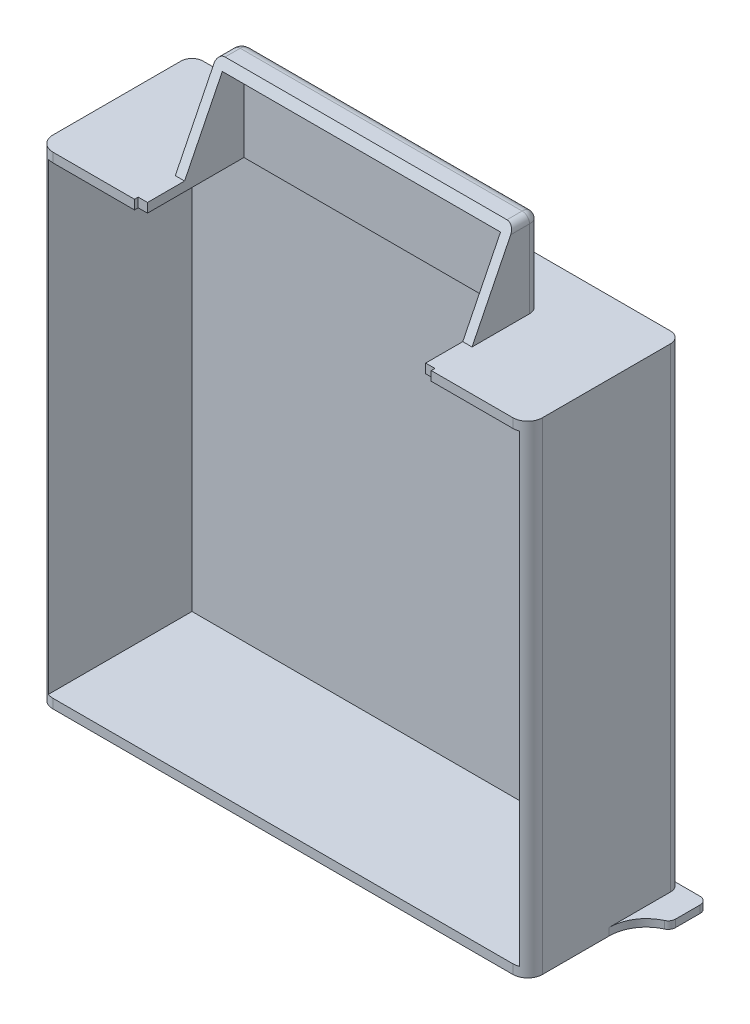
SolidWorks part; units mm, degrees
ref_plane "前视基准面" through (0, 0, 0) normal (0, 0, 1) x (1, 0, 0)
ref_plane "上视基准面" through (0, 0, 0) normal (0, 1, 0) x (1, 0, 0)
ref_plane "右视基准面" through (0, 0, 0) normal (1, 0, 0) x (0, 0, -1)
sketch "草图1" plane through (0, 0, 0) normal (0, 0, 1) x (1, 0, 0)
  line L1 (0, 0) -> (132, 0)
  line L2 (0, 0) -> (0, 130)
  line L3 (0, 130) -> (132, 130)
  line L4 (132, 0) -> (132, 130)
  line L5 (26, 130) -> (106, 130)
  line L6 (26, 130) -> (26, 153)
  line L7 (26, 153) -> (106, 153)
  line L8 (106, 130) -> (106, 153)
  point P9 (66, 153)
  point P10 (66, 130)
  dimension "D1" = 132
  dimension "D2" = 80
  dimension "D3" = 130
  dimension "D4" = 23
extrude "凸台-拉伸2" add sketch "草图1" along normal blind 41.5 contours L1 L4 L3 L2 region at (66, 65, 0)
extrude "凸台-拉伸3" add sketch "草图1<4>" along normal blind 20 from offset 12 contours L3 L8 L7 L6 region at (66, 141.5, 0)
sketch "草图1<4>" plane through (0, 0, 0) normal (0, 0, 1) x (1, 0, 0) same geometry as "草图1"
shell "抽壳1" thickness 2.5 removed face at (66, 141.5, 32) removed face at (66, 65, 41.5)
sketch "草图2" plane through (0, 130, 0) normal (0, 1, 0) x (1, 0, 0)
  line L0 (0, -41.5) -> (132, -41.5) construction
  line L1 (26, -32) -> (106, -32)
  line L2 (26, -32) -> (26, -41.5)
  line L3 (26, -41.5) -> (106, -41.5)
  line L4 (106, -32) -> (106, -41.5)
  line L5 (106, -32) -> (106, -12) construction
extrude "切除-拉伸1" cut sketch "草图2" against normal blind 20
sketch "草图4" plane through (0, 0, 0) normal (-1, 0, 0) x (0, 0, 1)
  line L1 (0, 0) -> (10, 0)
  line L2 (0, 0) -> (0, 2)
  line L3 (0, 2) -> (10, 2)
  line L4 (10, 0) -> (10, 2)
  dimension "D1" = 2
  dimension "D2" = 10
extrude "凸台-拉伸4" add sketch "草图4" along normal blind 7
fillet "圆角2" radius 10 1 edges at (0, 1, 10)
fillet "圆角3" radius 2 2 edges at (-7, 1, 0) (-7, 1, 10)
ref_plane "基准面1" through (66, 0, 0) normal (-1, 0, 0) x (0, 0, 1)
mirror "镜向1" about plane through (66, 0, 0) normal (-1, 0, 0) of bodies 110
fillet "圆角4" radius 2 2 edges at (106, 153, 22) (26, 153, 22)
fillet "圆角5" radius 4 2 edges at (132, 65, 41.5) (0, 65, 41.5)
sketch "草图5" plane through (0, 127.5, 0) normal (0, -1, 0) x (1, 0, 0)
  line L1 (26, 32) -> (28.5, 32)
  line L2 (26, 32) -> (26, 40.5)
  line L4 (28.5, 32) -> (28.5, 40.5)
  line L5 (28.5, 32) -> (26, 32) construction
  line L6 (26, 32) -> (26, 41.5) construction
  line L7 (28.5, 32) -> (28.5, 14.5) construction
  line L8 (26, 40.5) -> (28.5, 40.5)
  line L9 (4, 41.5) -> (26, 41.5) construction
  line L10 (66, 20.625) -> (66, -20.625) construction
  line L11 (106, 32) -> (103.5, 32)
  line L12 (106, 32) -> (106, 40.5)
  line L13 (106, 40.5) -> (103.5, 40.5)
  line L14 (103.5, 32) -> (103.5, 40.5)
  dimension "D1" = 1
extrude "凸台-拉伸5" add sketch "草图5" against normal blind 24.5
fillet "圆角6" [suppressed] radius 2
sketch "草图6" plane through (26, 0, 0) normal (-1, 0, 0) x (0, 0, 1)
  line L1 (40.5, 130) -> (30.5, 130)
  line L2 (18.5, 154.1712) -> (40.5, 155)
  line L3 (40.5, 155) -> (40.5, 130)
  line L4 (32, 152) -> (40.5, 152) construction
  line L5 (40.5, 130) -> (12, 130) construction
  line L6 (30.5, 130) -> (18.5, 154.1712)
  dimension "D1" = 22
  dimension "D2" = 25
  dimension "D3" = 10
extrude "切除-拉伸2" cut sketch "草图6" against normal through all
fillet "圆角7" radius 3 2 edges at (132, 66, 0) (0, 66, 0)
fillet "圆角8" radius 3 5 edges at (106, 140.5, 12) (105.4142, 152.4142, 12) (66, 153, 12) (26.5858, 152.4142, 12) (26, 140.5, 12)
